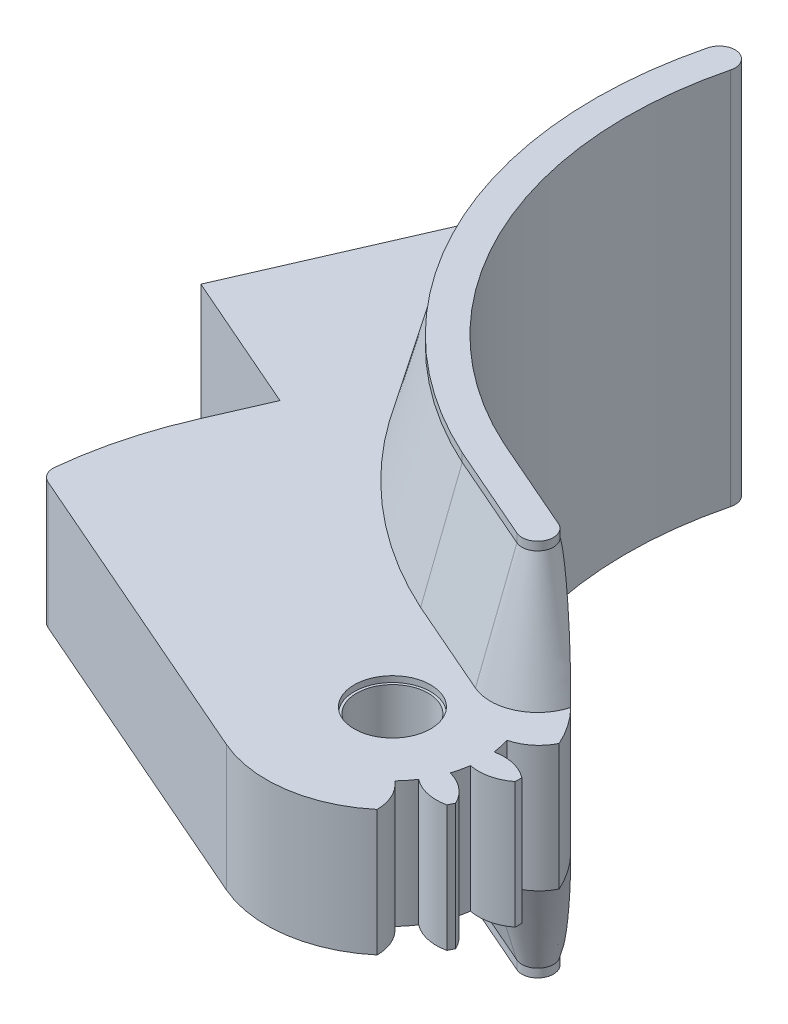
SolidWorks part; units mm, degrees
ref_plane "Plan de face" through (0, 0, 0) normal (0, 0, 1) x (1, 0, 0)
ref_plane "Plan de dessus" through (0, 0, 0) normal (0, 1, 0) x (1, 0, 0)
ref_plane "Plan de droite" through (0, 0, 0) normal (1, 0, 0) x (0, 0, -1)
sketch "Esquisse1" plane through (0, 0, 0) normal (0, 1, 0) x (1, 0, 0)
  line L0 (-21.1447, 0) -> (21.1447, 0) construction
  line L2 (0, 107.7631) -> (107.7631, 0) construction
  line L9 (0, 76.2) -> (0, -76.2) construction
  line L10 (22.4506, 85.3124) -> (49.3914, 112.2532) construction
  line L11 (112.2532, 49.3914) -> (49.3914, 112.2532) construction
  line L12 (85.3124, 22.4506) -> (22.4506, 85.3124) construction
  line L13 (85.3124, 22.4506) -> (112.2532, 49.3914) construction
  line L14 (0, 107.7631) -> (107.7631, 0) construction
  line L15 (0, -76.2) -> (0, -166.9225) construction
  line L16 (12.0681, -77.8609) -> (31.5678, -69.3535) construction
  line L17 (32.3819, -124.4225) -> (154.4572, -71.1636) construction
  line L18 (22.225, -101.1417) -> (-24.6748, 6.3579) construction
  line L19 (37.6806, 33.5622) -> (-24.6748, 6.3579) construction
  line L22 (31.5678, -69.3535) -> (134.1433, -24.602) construction
  line L26 (-73.8821, 18.6512) -> (13.4209, -19.4373) construction
  line L27 (-86.989, -59.0305) -> (-106.4228, -50.5519)
  line L28 (-37.6806, 33.5622) -> (24.6748, 6.3579) construction
  line L29 (-22.225, -101.1417) -> (24.6748, 6.3579) construction
  line L30 (-32.3819, -124.4225) -> (-96.1391, -96.6066)
  line L32 (73.8821, 18.6512) -> (-13.4209, -19.4373) construction
  line L33 (92.0675, -70.6709) -> (86.989, -59.0305) construction
  line L34 (86.989, -59.0305) -> (106.4228, -50.5519) construction
  line L35 (0, 107.7631) -> (-107.7631, 0) construction
  line L36 (-85.3124, 22.4506) -> (-112.2532, 49.3914) construction
  line L37 (-85.3124, 22.4506) -> (-22.4506, 85.3124) construction
  line L38 (-112.2532, 49.3914) -> (-49.3914, 112.2532) construction
  line L39 (-22.4506, 85.3124) -> (-49.3914, 112.2532) construction
  line L40 (0, 107.7631) -> (-107.7631, 0) construction
  line L41 (-92.0675, -70.6709) -> (-86.989, -59.0305)
  line L42 (-12.0681, -77.8609) -> (-31.5678, -69.3535)
  line L43 (22.225, -101.1417) -> (-22.225, -101.1417) construction
  circle A2 centre (22.225, -101.1417) radius 22.225 construction
  arc A3 (154.4572, -71.1636) -> (37.6806, 33.5622) centre (22.225, -101.1417) ccw construction
  circle A4 centre (22.225, -101.1417) radius 25.4 construction
  arc A5 (77.9162, -49.1327) -> (98.23, -95.6944) centre (22.225, -101.1417) cw construction
  arc A6 (112.8374, -33.8973) -> (117.7176, -4.8858) centre (0, 0) ccw construction
  arc A7 (115.5939, -2.8245) -> (117.557, -7.8522) centre (111.2211, -7.429) cw construction
  arc A8 (73.8821, 18.6512) -> (78.273, 22.3194) centre (76.9606, 19.4284) cw construction
  arc A14 (0, -76.2) -> (0, 76.2) centre (0, 0) ccw construction
  arc A17 (112.8374, -33.8973) -> (106.4228, -50.5519) centre (0, 0) cw construction
  arc A18 (-73.8821, 18.6512) -> (-78.273, 22.3194) centre (-76.9606, 19.4284) ccw
  arc A19 (-115.5939, -2.8245) -> (-117.557, -7.8522) centre (-111.2211, -7.429) ccw
  arc A20 (-112.8374, -33.8973) -> (-117.557, -7.8522) centre (0, 0) cw
  arc A21 (-92.0675, -70.6709) -> (-98.0279, -93.3728) centre (-22.225, -101.1417) ccw
  arc A22 (-12.0681, -77.8609) -> (-32.3819, -124.4225) centre (-22.225, -101.1417) cw
  arc A23 (-73.8821, 18.6512) -> (-31.5678, -69.3535) centre (0, 0) ccw
  circle A24 centre (-22.225, -101.1417) radius 22.225 construction
  arc A25 (-115.5939, -2.8245) -> (-78.273, 22.3194) centre (-22.225, -101.1417) cw
  arc A26 (-112.8374, -33.8973) -> (-106.4228, -50.5519) centre (0, 0) ccw
  circle A27 centre (94.8695, -93.6965) radius 3.175 construction
  arc A28 (-96.1391, -96.6066) -> (-98.0279, -93.3728) centre (-94.8695, -93.6965) cw
  dimension "D5" = 3.175
  dimension "D6" = 44.45
  dimension "D8" = 50.8
  dimension "D9" = 76.2
  dimension "D11" = 3.175
  dimension "D12" = 6.35
  dimension "D10" = 38.1
  dimension "D14" = 76.2
  dimension "D17" = 6.35
  dimension "D2" = 38.1
  dimension "D3" = 88.9
  dimension "D4" = 38.1
  dimension "D7" = 95.25
  dimension "D13" = 152.4
  dimension "D15" = 31.75
  dimension "D16" = 12.7
extrude "Boss.-Extru.1" add sketch "Esquisse1" along normal blind 25.4
sketch "Esquisse2" plane through (0, 25.4, 0) normal (0, 1, 0) x (1, 0, 0)
  line L3 (-12.0681, -77.8609) -> (-31.5678, -69.3535) construction
  line L6 (-12.0681, -77.8609) -> (-31.5678, -69.3535)
  line L7 (-14.6073, -83.6811) -> (-34.152, -75.1541)
  arc A3 (-73.8821, 18.6512) -> (-31.5678, -69.3535) centre (0, 0) ccw construction
  arc A9 (-73.8821, 18.6512) -> (-31.5678, -69.3535) centre (0, 0) ccw
  arc A10 (-80.039, 20.2055) -> (-34.152, -75.1541) centre (0, 0) ccw
  arc A11 (-73.8821, 18.6512) -> (-80.039, 20.2055) centre (-76.9606, 19.4284) ccw
  arc A12 (-12.0681, -77.8609) -> (-14.6073, -83.6811) centre (-13.3377, -80.771) cw
  dimension "D1" = 6.35
extrude "Boss.-Extru.3" add sketch "Esquisse2" along normal blind 25.4 and the other way blind 50.8
sketch "Esquisse4" plane through (0, 25.4, 0) normal (0, 1, 0) x (1, 0, 0)
  circle A0 centre (-22.225, -101.1417) radius 7.2
  arc A1 (-32.3819, -124.4225) -> (-12.0681, -77.8609) centre (-22.225, -101.1417) ccw construction
  dimension "D1" = 14.4
extrude "Enlèv. mat.-Extru.2" cut sketch "Esquisse4" against normal through all
sketch "Esquisse7" plane through (0, 0, 0) normal (0, 1, 0) x (-1, 0, 0)
  line L1 (-0.7984, 133.635) -> (-19.6267, 93.7248)
  line L3 (-19.6267, 93.7248) -> (-0.9424, 90.7287)
  line L4 (5.8699, 120.5754) -> (-0.7984, 133.635)
  circle A3 centre (22.225, 101.1417) radius 7.2 construction
  arc A115 (-0.3609, 89.5211) -> (6.9511, 91.1441) centre (1.548, 98.2037) ccw construction
  arc A116 (-0.9424, 90.7287) -> (-0.3609, 89.5211) centre (22.225, 101.1417) ccw construction
  arc A117 (4.8854, 95.4335) -> (-0.9424, 90.7287) centre (7.0361, 86.8076) ccw
  arc A118 (4.1259, 98.7612) -> (4.8854, 95.4335) centre (22.225, 101.1417) ccw
  arc A119 (-3.1662, 100.4715) -> (4.1259, 98.7612) centre (2.3209, 107.4661) ccw
  arc A120 (-3.1662, 101.8119) -> (-3.1662, 100.4715) centre (22.225, 101.1417) ccw
  arc A121 (4.1259, 103.5222) -> (-3.1662, 101.8119) centre (2.3209, 94.8173) ccw
  arc A122 (4.8854, 106.8499) -> (4.1259, 103.5222) centre (22.225, 101.1417) ccw
  arc A123 (-0.9424, 111.5547) -> (4.8854, 106.8499) centre (7.0361, 115.4758) ccw
  arc A124 (-0.3609, 112.7623) -> (-0.9424, 111.5547) centre (22.225, 101.1417) ccw
  arc A125 (6.9511, 111.1393) -> (-0.3609, 112.7623) centre (1.548, 104.0797) ccw
  arc A126 (9.0793, 113.808) -> (6.9511, 111.1393) centre (22.225, 101.1417) ccw
  arc A127 (5.8699, 120.5754) -> (9.0793, 113.808) centre (14.7596, 120.6465) ccw
  arc A128 (6.9178, 121.4111) -> (5.8699, 120.5754) centre (22.225, 101.1417) ccw construction
  arc A129 (12.8015, 116.7763) -> (6.9178, 121.4111) centre (4.8704, 112.7601) ccw construction
  arc A130 (15.8768, 118.2573) -> (12.8015, 116.7763) centre (22.225, 101.1417) ccw construction
  arc A131 (15.9216, 125.7471) -> (15.8768, 118.2573) centre (23.9617, 121.954) ccw construction
  arc A132 (17.2283, 126.0454) -> (15.9216, 125.7471) centre (22.225, 101.1417) ccw construction
  arc A133 (20.5183, 119.3167) -> (17.2283, 126.0454) centre (11.6301, 119.1394) ccw construction
  arc A134 (23.9317, 119.3167) -> (20.5183, 119.3167) centre (22.225, 101.1417) ccw construction
  arc A135 (27.2217, 126.0454) -> (23.9317, 119.3167) centre (32.8199, 119.1394) ccw construction
  arc A136 (28.5284, 125.7471) -> (27.2217, 126.0454) centre (22.225, 101.1417) ccw construction
  arc A137 (28.5732, 118.2573) -> (28.5284, 125.7471) centre (20.4883, 121.954) ccw construction
  arc A138 (31.6485, 116.7763) -> (28.5732, 118.2573) centre (22.225, 101.1417) ccw construction
  arc A139 (37.5322, 121.4111) -> (31.6485, 116.7763) centre (39.5796, 112.7601) ccw construction
  arc A140 (38.5801, 120.5754) -> (37.5322, 121.4111) centre (22.225, 101.1417) ccw construction
  arc A141 (35.3707, 113.808) -> (38.5801, 120.5754) centre (29.6904, 120.6465) ccw construction
  arc A142 (37.4989, 111.1393) -> (35.3707, 113.808) centre (22.225, 101.1417) ccw construction
  arc A143 (44.8109, 112.7623) -> (37.4989, 111.1393) centre (42.902, 104.0797) ccw construction
  arc A144 (45.3924, 111.5547) -> (44.8109, 112.7623) centre (22.225, 101.1417) ccw construction
  arc A145 (39.5646, 106.8499) -> (45.3924, 111.5547) centre (37.4139, 115.4758) ccw construction
  arc A146 (40.3241, 103.5222) -> (39.5646, 106.8499) centre (22.225, 101.1417) ccw construction
  arc A147 (47.6162, 101.8119) -> (40.3241, 103.5222) centre (42.1291, 94.8173) ccw construction
  arc A148 (47.6162, 100.4715) -> (47.6162, 101.8119) centre (22.225, 101.1417) ccw construction
  arc A149 (40.3241, 98.7612) -> (47.6162, 100.4715) centre (42.1291, 107.4661) ccw construction
  arc A150 (39.5646, 95.4335) -> (40.3241, 98.7612) centre (22.225, 101.1417) ccw construction
  arc A151 (45.3924, 90.7287) -> (39.5646, 95.4335) centre (37.4139, 86.8076) ccw construction
  arc A152 (44.8109, 89.5211) -> (45.3924, 90.7287) centre (22.225, 101.1417) ccw construction
  arc A153 (37.4989, 91.1441) -> (44.8109, 89.5211) centre (42.902, 98.2037) ccw construction
  arc A154 (35.3707, 88.4754) -> (37.4989, 91.1441) centre (22.225, 101.1417) ccw construction
  arc A155 (38.5801, 81.7079) -> (35.3707, 88.4754) centre (29.6904, 81.6369) ccw construction
  arc A156 (37.5322, 80.8722) -> (38.5801, 81.7079) centre (22.225, 101.1417) ccw construction
  arc A157 (31.6485, 85.507) -> (37.5322, 80.8722) centre (39.5796, 89.5233) ccw construction
  arc A158 (28.5732, 84.0261) -> (31.6485, 85.507) centre (22.225, 101.1417) ccw construction
  arc A159 (28.5284, 76.5363) -> (28.5732, 84.0261) centre (20.4883, 80.3294) ccw construction
  arc A160 (27.2217, 76.238) -> (28.5284, 76.5363) centre (22.225, 101.1417) ccw construction
  arc A161 (23.9317, 82.9667) -> (27.2217, 76.238) centre (32.8199, 83.144) ccw construction
  arc A162 (20.5183, 82.9667) -> (23.9317, 82.9667) centre (22.225, 101.1417) ccw construction
  arc A163 (17.2283, 76.238) -> (20.5183, 82.9667) centre (11.6301, 83.144) ccw construction
  arc A164 (15.9216, 76.5363) -> (17.2283, 76.238) centre (22.225, 101.1417) ccw construction
  arc A165 (15.8768, 84.0261) -> (15.9216, 76.5363) centre (23.9617, 80.3294) ccw construction
  arc A166 (12.8015, 85.507) -> (15.8768, 84.0261) centre (22.225, 101.1417) ccw construction
  arc A167 (6.9178, 80.8722) -> (12.8015, 85.507) centre (4.8704, 89.5233) ccw construction
  arc A168 (5.8699, 81.7079) -> (6.9178, 80.8722) centre (22.225, 101.1417) ccw construction
  arc A169 (9.0793, 88.4754) -> (5.8699, 81.7079) centre (14.7596, 81.6369) ccw construction
  arc A170 (6.9511, 91.1441) -> (9.0793, 88.4754) centre (22.225, 101.1417) ccw construction
sketch "Esquisse11" plane through (0, 0, 0) normal (0, -1, 0) x (1, 0, 0)
  arc A0 (-41.6588, 84.7866) -> (-34.8913, 87.996) centre (-41.7298, 93.6763) ccw
  arc A1 (-42.4945, 85.8345) -> (-41.6588, 84.7866) centre (-22.225, 101.1417) ccw
  arc A2 (-37.8596, 91.7182) -> (-42.4945, 85.8345) centre (-33.8434, 83.7871) ccw
  arc A3 (-39.3406, 94.7935) -> (-37.8596, 91.7182) centre (-22.225, 101.1417) ccw
  arc A4 (-46.8304, 94.8382) -> (-39.3406, 94.7935) centre (-43.0373, 102.8784) ccw
  arc A5 (-47.1287, 96.145) -> (-46.8304, 94.8382) centre (-22.225, 101.1417) ccw
  arc A6 (-40.4, 99.435) -> (-47.1287, 96.145) centre (-40.2227, 90.5468) ccw
  arc A7 (-40.4, 102.8483) -> (-40.4, 99.435) centre (-22.225, 101.1417) ccw
  arc A8 (-47.1287, 106.1384) -> (-40.4, 102.8483) centre (-40.2227, 111.7366) ccw
  arc A9 (-46.8304, 107.4451) -> (-47.1287, 106.1384) centre (-22.225, 101.1417) ccw
  arc A10 (-39.3406, 107.4899) -> (-46.8304, 107.4451) centre (-43.0373, 99.4049) ccw
  arc A11 (-37.8596, 110.5652) -> (-39.3406, 107.4899) centre (-22.225, 101.1417) ccw
  arc A12 (-42.4945, 116.4489) -> (-37.8596, 110.5652) centre (-33.8434, 118.4963) ccw
  arc A13 (-41.6588, 117.4968) -> (-42.4945, 116.4489) centre (-22.225, 101.1417) ccw
  arc A14 (-34.8913, 114.2874) -> (-41.6588, 117.4968) centre (-41.7298, 108.6071) ccw
  arc A15 (-32.2226, 116.4156) -> (-34.8913, 114.2874) centre (-22.225, 101.1417) ccw
  arc A16 (-33.8456, 123.7276) -> (-32.2226, 116.4156) centre (-25.163, 121.8187) ccw
  arc A17 (-32.638, 124.3091) -> (-33.8456, 123.7276) centre (-22.225, 101.1417) ccw
  arc A18 (-27.9332, 118.4813) -> (-32.638, 124.3091) centre (-36.5591, 116.3306) ccw
  arc A19 (-24.6055, 119.2408) -> (-27.9332, 118.4813) centre (-22.225, 101.1417) ccw
  arc A20 (-22.8952, 126.5328) -> (-24.6055, 119.2408) centre (-15.9006, 121.0458) ccw
  arc A21 (-21.5548, 126.5328) -> (-22.8952, 126.5328) centre (-22.225, 101.1417) ccw
  arc A22 (-19.8445, 119.2408) -> (-21.5548, 126.5328) centre (-28.5494, 121.0458) ccw
  arc A23 (-16.5168, 118.4813) -> (-19.8445, 119.2408) centre (-22.225, 101.1417) ccw
  arc A24 (-11.812, 124.3091) -> (-16.5168, 118.4813) centre (-7.8909, 116.3306) ccw
  arc A25 (-10.6044, 123.7276) -> (-11.812, 124.3091) centre (-22.225, 101.1417) ccw
  arc A26 (-12.2274, 116.4156) -> (-10.6044, 123.7276) centre (-19.287, 121.8187) ccw
  arc A27 (-9.5587, 114.2874) -> (-12.2274, 116.4156) centre (-22.225, 101.1417) ccw
  arc A28 (-2.7912, 117.4968) -> (-9.5587, 114.2874) centre (-2.7202, 108.6071) ccw
  arc A29 (-1.9555, 116.4489) -> (-2.7912, 117.4968) centre (-22.225, 101.1417) ccw
  arc A30 (-6.5904, 110.5652) -> (-1.9555, 116.4489) centre (-10.6066, 118.4963) ccw
  arc A31 (-5.1094, 107.4899) -> (-6.5904, 110.5652) centre (-22.225, 101.1417) ccw
  arc A32 (2.3804, 107.4451) -> (-5.1094, 107.4899) centre (-1.4127, 99.4049) ccw
  arc A33 (2.6787, 106.1384) -> (2.3804, 107.4451) centre (-22.225, 101.1417) ccw
  arc A34 (-4.05, 102.8483) -> (2.6787, 106.1384) centre (-4.2273, 111.7366) ccw
  arc A35 (-4.05, 99.435) -> (-4.05, 102.8483) centre (-22.225, 101.1417) ccw
  arc A36 (2.6787, 96.145) -> (-4.05, 99.435) centre (-4.2273, 90.5468) ccw
  arc A37 (2.3804, 94.8382) -> (2.6787, 96.145) centre (-22.225, 101.1417) ccw
  arc A38 (-5.1094, 94.7935) -> (2.3804, 94.8382) centre (-1.4127, 102.8784) ccw
  arc A39 (-6.5904, 91.7182) -> (-5.1094, 94.7935) centre (-22.225, 101.1417) ccw
  arc A40 (-1.9555, 85.8345) -> (-6.5904, 91.7182) centre (-10.6066, 83.7871) ccw
  arc A41 (-2.7912, 84.7866) -> (-1.9555, 85.8345) centre (-22.225, 101.1417) ccw
  arc A42 (-9.5587, 87.996) -> (-2.7912, 84.7866) centre (-2.7202, 93.6763) ccw
  arc A43 (-12.2274, 85.8678) -> (-9.5587, 87.996) centre (-22.225, 101.1417) ccw
  arc A44 (-10.6044, 78.5558) -> (-12.2274, 85.8678) centre (-19.287, 80.4647) ccw
  arc A45 (-11.812, 77.9743) -> (-10.6044, 78.5558) centre (-22.225, 101.1417) ccw
  arc A46 (-16.5168, 83.8021) -> (-11.812, 77.9743) centre (-7.8909, 85.9528) ccw
  arc A47 (-19.8445, 83.0426) -> (-16.5168, 83.8021) centre (-22.225, 101.1417) ccw
  arc A48 (-21.5548, 75.7505) -> (-19.8445, 83.0426) centre (-28.5494, 81.2376) ccw
  arc A49 (-22.8952, 75.7505) -> (-21.5548, 75.7505) centre (-22.225, 101.1417) ccw
  arc A50 (-24.6055, 83.0426) -> (-22.8952, 75.7505) centre (-15.9006, 81.2376) ccw
  arc A51 (-27.9332, 83.8021) -> (-24.6055, 83.0426) centre (-22.225, 101.1417) ccw
  arc A52 (-32.638, 77.9743) -> (-27.9332, 83.8021) centre (-36.5591, 85.9528) ccw
  arc A53 (-33.8456, 78.5558) -> (-32.638, 77.9743) centre (-22.225, 101.1417) ccw
  arc A54 (-32.2226, 85.8678) -> (-33.8456, 78.5558) centre (-25.163, 80.4647) ccw
  arc A55 (-34.8913, 87.996) -> (-32.2226, 85.8678) centre (-22.225, 101.1417) ccw
extrude "Enlèv. mat.-Extru.6" cut sketch "Esquisse7" along normal through all
chamfer "Chanfrein1" distance 6.35 angle 75 4 edges at (-10.4276, 0, 82.0406) (-79.3972, 0, -21.4639) (-24.3797, 0, 79.4176) (-74.3859, 0, 35.7944) first distance on face at (-22.225, 0, 108.3417)
chamfer "Chanfrein2" distance 6.35 angle 75 4 edges at (-79.3972, 25.4, -21.4639) (-10.4276, 25.4, 82.0406) (-74.3859, 25.4, 35.7944) (-24.3797, 25.4, 79.4176) first distance on face at (-22.225, 25.4, 108.3417)
sketch "Esquisse12" plane through (0, 25.4, 0) normal (0, 1, 0) x (1, 0, 0)
  circle A0 centre (-22.225, -101.1417) radius 7.7
  dimension "D1" = 15.4
extrude "Enlèv. mat.-Extru.7" cut sketch "Esquisse12" against normal blind 1.2
sketch "Esquisse13" plane through (0, 0, 0) normal (0, -1, 0) x (1, 0, 0)
  circle A0 centre (-22.225, 101.1417) radius 7.7
  dimension "D1" = 15.4
extrude "Enlèv. mat.-Extru.8" cut sketch "Esquisse13" against normal blind 1.2
sketch "Esquisse14" plane through (0, 0, 0) normal (0, -1, 0) x (1, 0, 0)
  line L0 (-106.4228, 50.5519) -> (-132.0793, 39.3585)
  line L1 (-132.0793, 39.3585) -> (-104.888, -22.967)
  line L2 (-104.888, -22.967) -> (-87.0724, -17.9332)
  line L3 (-87.0724, -17.9332) -> (-106.4228, 50.5519)
  line L4 (-106.4228, 50.5519) -> (-86.989, 59.0305) construction
  arc A0 (-117.557, 7.8522) -> (-115.5939, 2.8245) centre (-111.2211, 7.429) ccw construction
extrude "Boss.-Extru.4" add sketch "Esquisse14" against normal blind 25.4
sketch "Esquisse15" plane through (0, 0, 0) normal (0, -1, 0) x (1, 0, 0)
  line L0 (-87.0724, -17.9332) -> (-115.2676, 46.6931)
  line L1 (-132.0793, 39.3585) -> (-86.989, 59.0305) construction
  line L2 (-115.2676, 46.6931) -> (-162.6801, 43.435)
  line L3 (-162.6801, 43.435) -> (-124.784, -58.9279)
  line L4 (-124.784, -58.9279) -> (-87.0724, -17.9332)
extrude "Enlèv. mat.-Extru.9" cut sketch "Esquisse15" against normal through all
